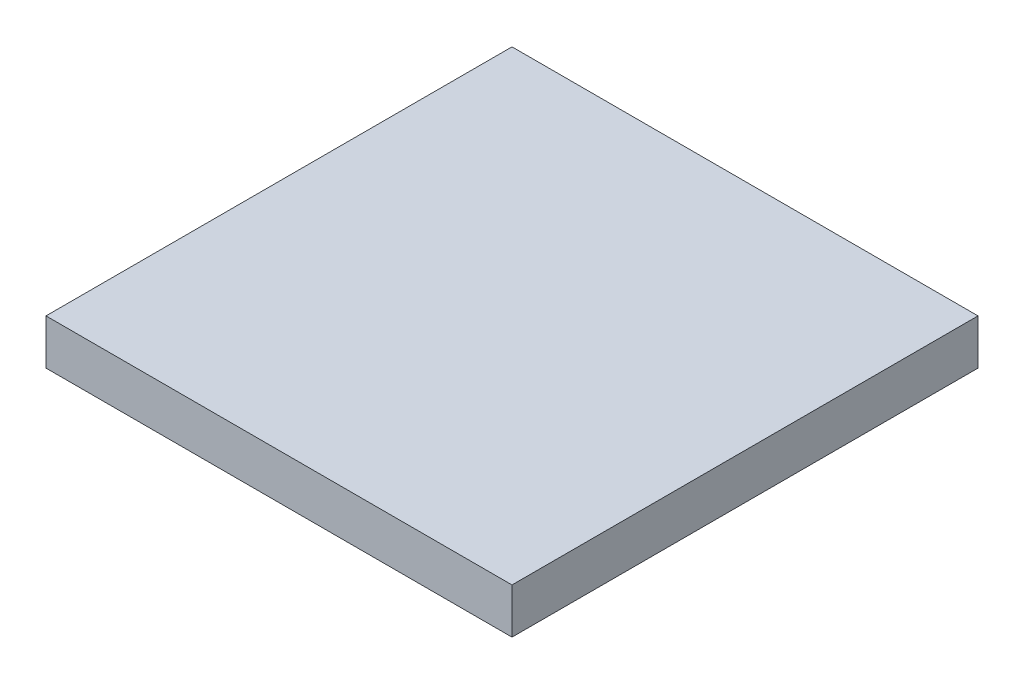
SolidWorks part; units mm, degrees
ref_plane "Front Plane" through (0, 0, 0) normal (0, 0, 1) x (1, 0, 0)
ref_plane "Top Plane" through (0, 0, 0) normal (0, 1, 0) x (1, 0, 0)
ref_plane "Right Plane" through (0, 0, 0) normal (1, 0, 0) x (0, 0, -1)
sketch "Sketch1" plane through (0, 0, 0) normal (0, 1, 0) x (1, 0, 0)
  line L1 (-5.15, -5.15) -> (5.15, -5.15)
  line L2 (-5.15, -5.15) -> (-5.15, 5.15)
  line L3 (-5.15, 5.15) -> (5.15, 5.15)
  line L4 (5.15, -5.15) -> (5.15, 5.15)
  line L5 (-5.15, -5.15) -> (5.15, 5.15) construction
  line L6 (-5.15, 5.15) -> (5.15, -5.15) construction
  point P0 (0, 0)
  dimension "D1" = 10.3
  dimension "D2" = 10.3
extrude "chip_lid" add sketch "Sketch1" along normal blind 1
equation "\"pcb_length\"= 40 ' length of the chip in the direction of the feadline"
equation "\"pcb_side\"= 40    ' length of the chip in the other direction"
equation "\"pcb_width\"= 1"
equation "\"wall_width\"= 1  ' minimal width from the box walls"
equation "\"route_width\"= 1 ' The width of the trace on the lid for not touching the signal roates."
equation "\"route_clearence\"= 0.4 ' The clearence depth of the trace on the lid for not touching the signal roates."
equation "\"route_chip_clearence\"= 1"
equation "\"port_count\"= 6"
equation "\"port_space\"= 1.5"
equation "\"port_length\"= 5.1"
equation "\"port_width\"= 5.1"
equation "\"chip_length\"= 6.3 ' length of the chip in the direction of the feadline"
equation "\"chip_side\"= 6.3 ' length of the chip in the other direction"
equation "\"pedestal_depth\"= 2 ' depth of the pedestal under the chip"
equation "\"chip_leg\"= 0.8  ' size of the legs the chip lay on in case there is pedestal"
equation "\"wing_length\"= 10 ' Mounting wing size"
equation "\"wing_width\"= 1 ' mounting wing width"
equation "\"bonding_clearence\"= 1"
equation "\"box_height\"= \"wall_width\" + \"pedestal_depth\" + \"pcb_width\""
equation "\"box_length\"= \"pcb_length\" + 2 * \"wall_width\""
equation "\"box_side\"= \"pcb_side\" + 2 * \"wall_width\""
equation "\"D1@Sketch1\"=\"chip_length\"+2*\"wall_width\"+2*\"bonding_clearence\""
equation "\"D1@chip_lid\"=\"wall_width\""
equation "\"D2@Sketch1\"=\"chip_side\"+2*\"wall_width\"+2*\"bonding_clearence\""
equation "\"chip_width\"= 0.4 ' width of the chip"
